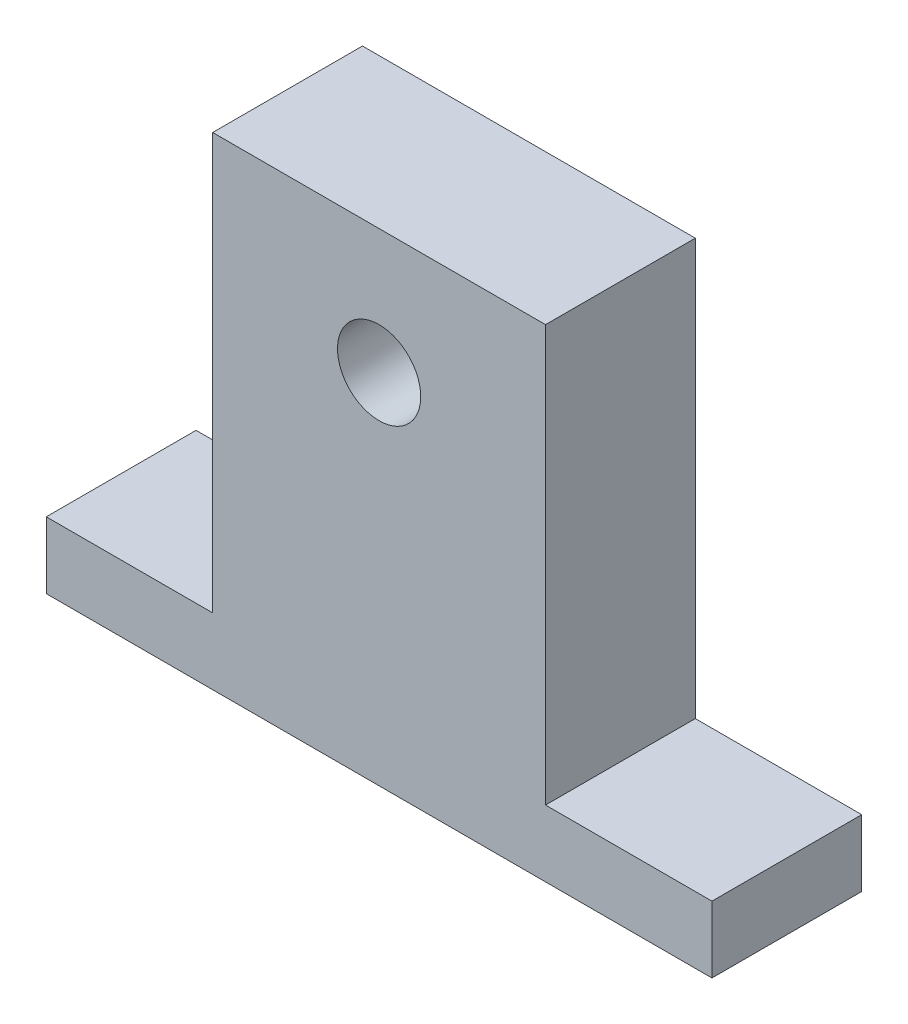
SolidWorks part; units mm, degrees
ref_plane "Plan de face" through (0, 0, 0) normal (0, 0, 1) x (1, 0, 0)
ref_plane "Plan de dessus" through (0, 0, 0) normal (0, 1, 0) x (1, 0, 0)
ref_plane "Plan de droite" through (0, 0, 0) normal (1, 0, 0) x (0, 0, -1)
sketch "Esquisse1" plane through (0, 0, 0) normal (0, 0, 1) x (1, 0, 0)
  line L0 (-40, 0) -> (-80, 0)
  line L1 (-80, 0) -> (-80, 4)
  line L2 (-80, 4) -> (-70, 4)
  line L3 (-70, 4) -> (-70, 29)
  line L4 (-70, 29) -> (-50, 29)
  line L5 (-50, 29) -> (-50, 4)
  line L6 (-50, 4) -> (-40, 4)
  line L7 (-40, 4) -> (-40, 0)
  circle A0 centre (-60, 21.5) radius 2.5
  dimension "D10" = 5
  dimension "D1" = 40
  dimension "D2" = 10
  dimension "D3" = 10
  dimension "D4" = 40
  dimension "D5" = 25
  dimension "D6" = 4
  dimension "D7" = 4
  dimension "D8" = 7.5
  dimension "D9" = 10
extrude "Boss.-Extru.2" add sketch "Esquisse1" against normal blind 9 contours L4 L5 L6 L7 L0 L1 L2 L3
sketch3d "Esquisse3D1"
  point P3 (-95.2387, 3.6789, 0)
extrude "Enlèv. mat.-Extru.6" cut sketch "Esquisse1<4>" against normal through all contours A0
sketch "Esquisse1<4>" plane through (0, 0, 0) normal (0, 0, 1) x (1, 0, 0) same geometry as "Esquisse1"
